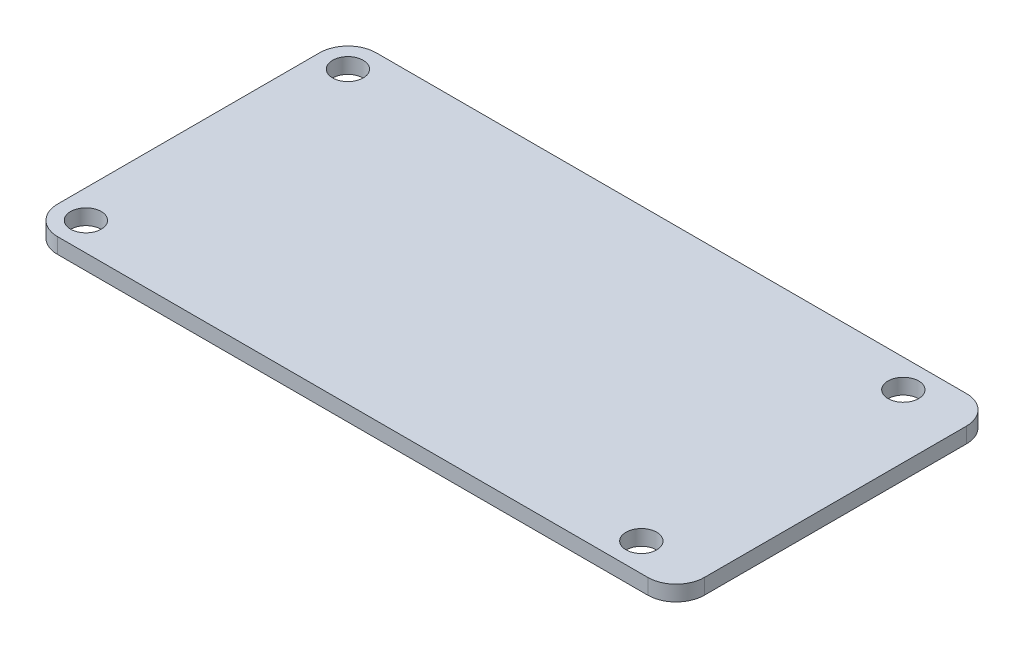
SolidWorks part; units mm, degrees
ref_plane "Front Plane" through (0, 0, 0) normal (0, 0, 1) x (1, 0, 0)
ref_plane "Top Plane" through (0, 0, 0) normal (0, 1, 0) x (1, 0, 0)
ref_plane "Right Plane" through (0, 0, 0) normal (1, 0, 0) x (0, 0, -1)
sketch "Sketch1" plane through (0, 0, 0) normal (0, 1, 0) x (1, 0, 0)
  line L0 (0, 0) -> (0, 27.9326) construction
  line L1 (-33.5, 13.57) -> (-33.5, -13.57)
  line L2 (-30.57, 16.5) -> (30.57, 16.5)
  line L3 (33.5, 13.57) -> (33.5, -13.57)
  line L4 (-30.57, -16.5) -> (30.57, -16.5)
  line L5 (0, 0) -> (-51.5102, 0) construction
  line L6 (-30.57, 13.57) -> (26.97, 13.57) construction
  line L7 (-30.57, 13.57) -> (-30.57, -13.57) construction
  line L8 (-30.57, -13.57) -> (26.97, -13.57) construction
  line L9 (26.97, 13.57) -> (26.97, -13.57) construction
  circle A0 centre (-30.57, 13.57) radius 1.5875
  circle A1 centre (26.97, 13.57) radius 1.5875
  circle A2 centre (26.97, -13.57) radius 1.5875
  circle A3 centre (-30.57, -13.57) radius 1.5875
  arc A4 (-33.5, 13.57) -> (-30.57, 16.5) centre (-30.57, 13.57) cw
  arc A5 (30.57, 16.5) -> (33.5, 13.57) centre (30.57, 13.57) cw
  arc A6 (33.5, -13.57) -> (30.57, -16.5) centre (30.57, -13.57) cw
  arc A7 (-30.57, -16.5) -> (-33.5, -13.57) centre (-30.57, -13.57) cw
  point P4 (-33.5, 0)
  point P6 (0, 0)
  point P7 (0, 0)
  point P26 (26.97, -13.57)
  point P27 (26.97, 13.57)
  point P28 (-30.697, -13.697)
  point P29 (0, 16.5)
  point P30 (-30.697, -13.697)
  point P31 (0, 0)
  point P32 (0, 0)
  dimension "D6" = 3.175
  dimension "D5" = 2.93
  dimension "D1" = 33
  dimension "D2" = 67
  dimension "D3" = 27.14
  dimension "D4" = 57.54
extrude "Boss-Extrude1" add sketch "Sketch1" along normal blind 1.6
